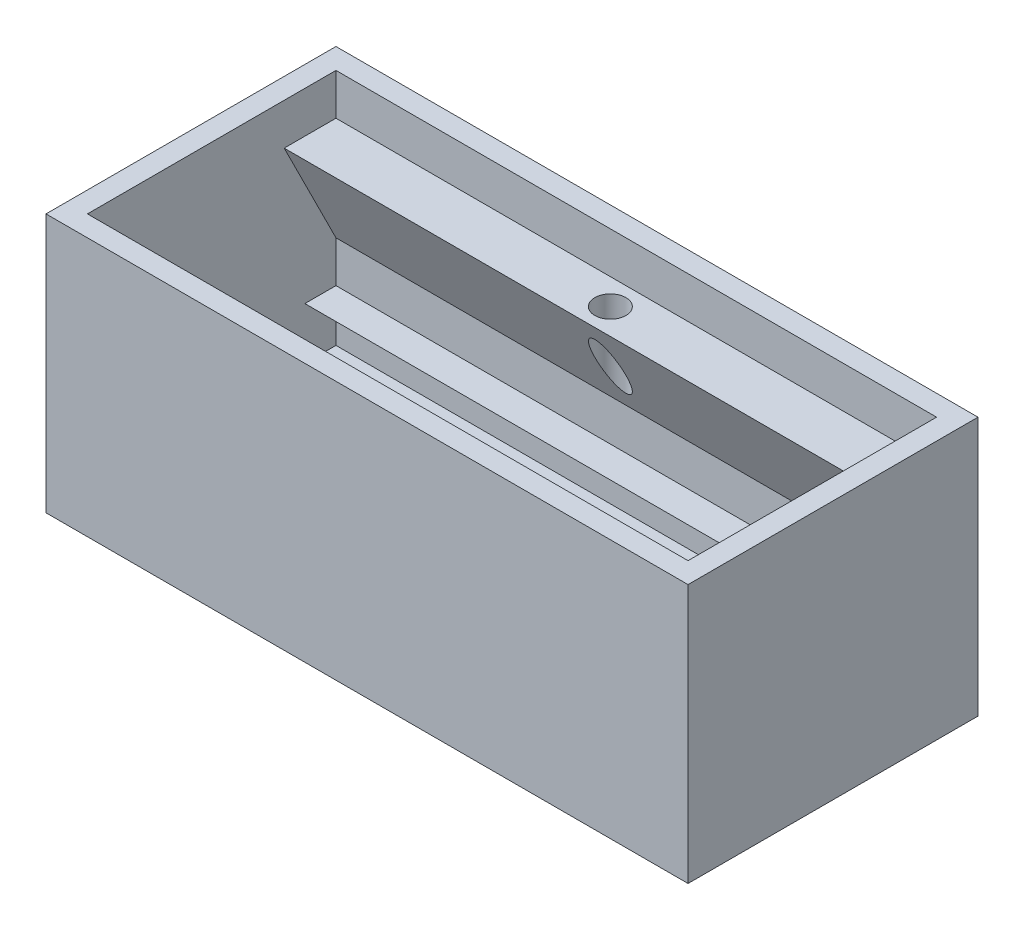
SolidWorks part; units mm, degrees
ref_plane "Front" through (0, 0, 0) normal (0, 0, 1) x (1, 0, 0)
ref_plane "Top" through (0, 0, 0) normal (0, 1, 0) x (1, 0, 0)
ref_plane "Right" through (0, 0, 0) normal (1, 0, 0) x (0, 0, -1)
sketch "Sketch1" plane through (0, 0, 0) normal (0, 1, 0) x (1, 0, 0)
  line L1 (0, 0) -> (62, 0)
  line L2 (0, 0) -> (0, 28)
  line L3 (0, 28) -> (62, 28)
  line L4 (62, 0) -> (62, 28)
  dimension "D1" = 62
  dimension "D2" = 28
extrude "Boss-Extrude1" add sketch "Sketch1" along normal blind 25
sketch "Sketch2" plane through (0, 25, 0) normal (0, 1, 0) x (1, 0, 0)
  line L0 (0, 28) -> (0, 0) construction
  line L1 (2, 26) -> (60, 26)
  line L2 (2, 26) -> (2, 2)
  line L3 (2, 2) -> (60, 2)
  line L4 (60, 26) -> (60, 2)
  line L5 (62, 28) -> (0, 28) construction
  line L6 (62, 0) -> (62, 28) construction
  line L7 (0, 0) -> (62, 0) construction
  dimension "D1" = 2
  dimension "D2" = 2
  dimension "D3" = 2
  dimension "D4" = 2
extrude "Cut-Extrude1" cut sketch "Sketch2" against normal blind 23
sketch "Sketch3" plane through (2, 0, 0) normal (1, 0, 0) x (0, 0, -1)
  line L0 (26, 11) -> (21, 21)
  line L1 (26, 2) -> (26, 25) construction
  line L2 (21, 21) -> (26, 21)
  line L3 (26, 21) -> (26, 11)
  line L4 (0, 25) -> (28, 25) construction
  dimension "D1" = 5
  dimension "D2" = 10
  dimension "D3" = 4
extrude "Boss-Extrude3" add sketch "Sketch3" along normal up to surface (58 mm away) up to face at (60, 13.5, -14)
hole_wizard "Ø1.0 (1) Diameter Hole1" positions "Sketch5" profile "Sketch4" hole size "Ø1.0" standard "ANSI Metric" end condition up to next
sketch "Sketch5" plane through (0, 0, 0) normal (0, -1, 0) x (-1, 0, 0)
  line L0 (0, 0) -> (-62, 0) construction
  line L1 (0, 28) -> (0, 0) construction
  point P0 (-7.5, 7.5)
  point P2 (-5.5, 7.5)
  point P4 (-3.5, 7.5)
  dimension "D1" = 7.5
  dimension "D2" = 3.5
  dimension "D3" = 2
  dimension "D4" = 2
sketch "Sketch4" plane through (7.5, 0, -7.5) normal (1, 0, 0) x (0, 0, -1)
  line L0 (0, 0) -> (0, 2)
  line L1 (0, 2) -> (0.5, 2)
  line L2 (0.5, 2) -> (0.5, 0)
  line L5 (0.5, 0) -> (0, 0)
  line L11 (0, -6.35) -> (0, 107.95) construction
  dimension "Thru Hole Dia." = 1
  dimension "Thru Hole Depth" = 2
hole_wizard "Ø2.0 (2) Diameter Hole1" positions "Sketch7" profile "Sketch6" hole size "Ø2.0" standard "ANSI Metric" end condition up to next
sketch "Sketch7" plane through (0, 0, 0) normal (0, -1, 0) x (-1, 0, 0)
  line L0 (-62, 0) -> (-62, 28) construction
  line L1 (0, 0) -> (-62, 0) construction
  point P0 (-53, 21)
  dimension "D1" = 9
  dimension "D2" = 21
sketch "Sketch6" plane through (53, 0, -21) normal (1, 0, 0) x (0, 0, -1)
  line L0 (0, 0) -> (0, 2)
  line L1 (0, 2) -> (1, 2)
  line L2 (1, 2) -> (1, 0)
  line L5 (1, 0) -> (0, 0)
  line L11 (0, -6.35) -> (0, 107.95) construction
  dimension "Thru Hole Dia." = 2
  dimension "Thru Hole Depth" = 2
hole_wizard "Ø3.5 (3.5) Diameter Hole1" positions "Sketch9" profile "Sketch8" hole size "Ø3.5" standard "ANSI Metric" end condition up to next
sketch "Sketch9" plane through (0, 0, 0) normal (0, -1, 0) x (-1, 0, 0)
  line L0 (0, 0) -> (-62, 0) construction
  line L1 (-62, 0) -> (-62, 28) construction
  point P0 (-40, 22)
  dimension "D1" = 22
  dimension "D2" = 22
sketch "Sketch8" plane through (40, 0, -22) normal (1, 0, 0) x (0, 0, -1)
  line L0 (0, 0) -> (0, 2)
  line L1 (0, 2) -> (1.75, 2)
  line L2 (1.75, 2) -> (1.75, 0)
  line L5 (1.75, 0) -> (0, 0)
  line L11 (0, -6.35) -> (0, 107.95) construction
  dimension "Thru Hole Dia." = 3.5
  dimension "Thru Hole Depth" = 2
sketch "Sketch10" plane through (2, 0, 0) normal (1, 0, 0) x (0, 0, -1)
  line L0 (26, 4) -> (23, 7)
  line L1 (26, 2) -> (26, 11) construction
  line L2 (23, 7) -> (26, 7)
  line L3 (26, 7) -> (26, 4)
  dimension "D1" = 2
  dimension "D2" = 3
  dimension "D3" = 3
extrude "Boss-Extrude4" add sketch "Sketch10" along normal up to next
hole_wizard "Ø3.0 (3) Diameter Hole1" positions "Sketch12" profile "Sketch11" hole size "Ø3.0" standard "ANSI Metric" end condition up to next
sketch "Sketch12" plane through (0, 21, 0) normal (0, 1, 0) x (1, 0, 0)
  line L0 (60, 26) -> (2, 26) construction
  line L1 (2, 26) -> (2, 21) construction
  point P0 (31, 23.5)
  dimension "D1" = 2.5
  dimension "D2" = 29
sketch "Sketch11" plane through (31, 21, -23.5) normal (1, 0, 0) x (0, 0, 1)
  line L0 (0, 0) -> (0, 5)
  line L1 (0, 5) -> (1.5, 5)
  line L2 (1.5, 5) -> (1.5, 0)
  line L5 (1.5, 0) -> (0, 0)
  line L11 (0, -6.35) -> (0, 107.95) construction
  dimension "Thru Hole Dia." = 3
  dimension "Thru Hole Depth" = 5
